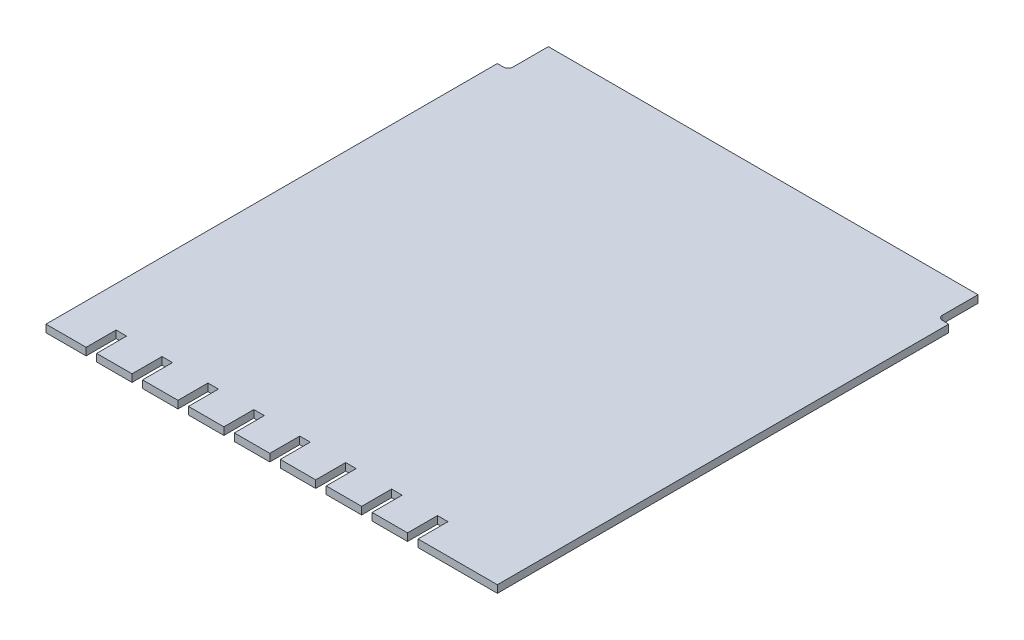
SolidWorks part; units mm, degrees
ref_plane "Front Plane" through (0, 0, 0) normal (0, 0, 1) x (1, 0, 0)
ref_plane "Top Plane" through (0, 0, 0) normal (0, 1, 0) x (1, 0, 0)
ref_plane "Right Plane" through (0, 0, 0) normal (1, 0, 0) x (0, 0, -1)
sketch "Sketch1" plane through (0, 0, 0) normal (0, 1, 0) x (1, 0, 0)
  line L0 (4.5, 96.6) -> (4.5, 104.1)
  line L1 (2.2, 0) -> (97.8, 0) construction
  line L2 (4.5, 104.1) -> (95.5, 104.1)
  line L3 (2.2, 95.6) -> (97.8, 95.6) construction
  line L4 (95.5, 104.1) -> (95.5, 96.6)
  line L5 (2.2, 95.6) -> (3.5, 95.6)
  line L6 (96.5, 95.6) -> (97.8, 95.6)
  line L7 (10.7, 0) -> (10.7, 6.3449)
  line L8 (10.7, 6.3449) -> (12.925, 6.3449)
  line L9 (12.925, 6.3449) -> (12.925, 0)
  line L10 (12.925, 0) -> (20.425, 0)
  line L11 (20.425, 0) -> (20.425, 6.3449)
  line L12 (20.425, 6.3449) -> (22.65, 6.3449)
  line L13 (22.65, 6.3449) -> (22.65, 0)
  line L14 (22.65, 0) -> (30.15, 0)
  line L15 (30.15, 0) -> (30.15, 6.3449)
  line L16 (2.2, 0) -> (2.2, 95.6)
  line L17 (30.15, 6.3449) -> (32.375, 6.3449)
  line L18 (97.8, 0) -> (97.8, 95.6)
  line L19 (32.375, 6.3449) -> (32.375, 0)
  line L20 (32.375, 0) -> (39.875, 0)
  line L21 (2.2, 0) -> (10.7, 0)
  line L22 (39.875, 0) -> (39.875, 6.3449)
  line L23 (39.875, 6.3449) -> (42.1, 6.3449)
  line L24 (42.1, 6.3449) -> (42.1, 0)
  line L25 (42.1, 0) -> (49.6, 0)
  line L26 (49.6, 0) -> (49.6, 6.3449)
  line L27 (49.6, 6.3449) -> (51.825, 6.3449)
  line L28 (51.825, 6.3449) -> (51.825, 0)
  line L29 (51.825, 0) -> (59.325, 0)
  line L30 (59.325, 0) -> (59.325, 6.3449)
  line L31 (59.325, 6.3449) -> (61.55, 6.3449)
  line L32 (61.55, 6.3449) -> (61.55, 0)
  line L33 (61.55, 0) -> (69.05, 0)
  line L34 (69.05, 0) -> (69.05, 6.3449)
  line L35 (69.05, 6.3449) -> (71.275, 6.3449)
  line L36 (71.275, 6.3449) -> (71.275, 0)
  line L37 (71.275, 0) -> (78.775, 0)
  line L38 (78.775, 0) -> (78.775, 6.3449)
  line L39 (78.775, 6.3449) -> (81, 6.3449)
  line L40 (81, 6.3449) -> (81, 0)
  line L41 (81, 0) -> (97.8, 0)
  arc A0 (95.5, 96.6) -> (96.5, 95.6) centre (96.5, 96.6) ccw
  arc A1 (4.5, 96.6) -> (3.5, 95.6) centre (3.5, 96.6) cw
  point P8 (95.5, 95.6)
  point P11 (4.5, 95.6)
  dimension "D1" = 1
extrude "Boss-Extrude1" add sketch "Sketch1" along normal blind 1.5875
ref_plane "center-of-slot" through (0, 0.7937, 0) normal (0, 1, 0) x (1, 0, 0)
